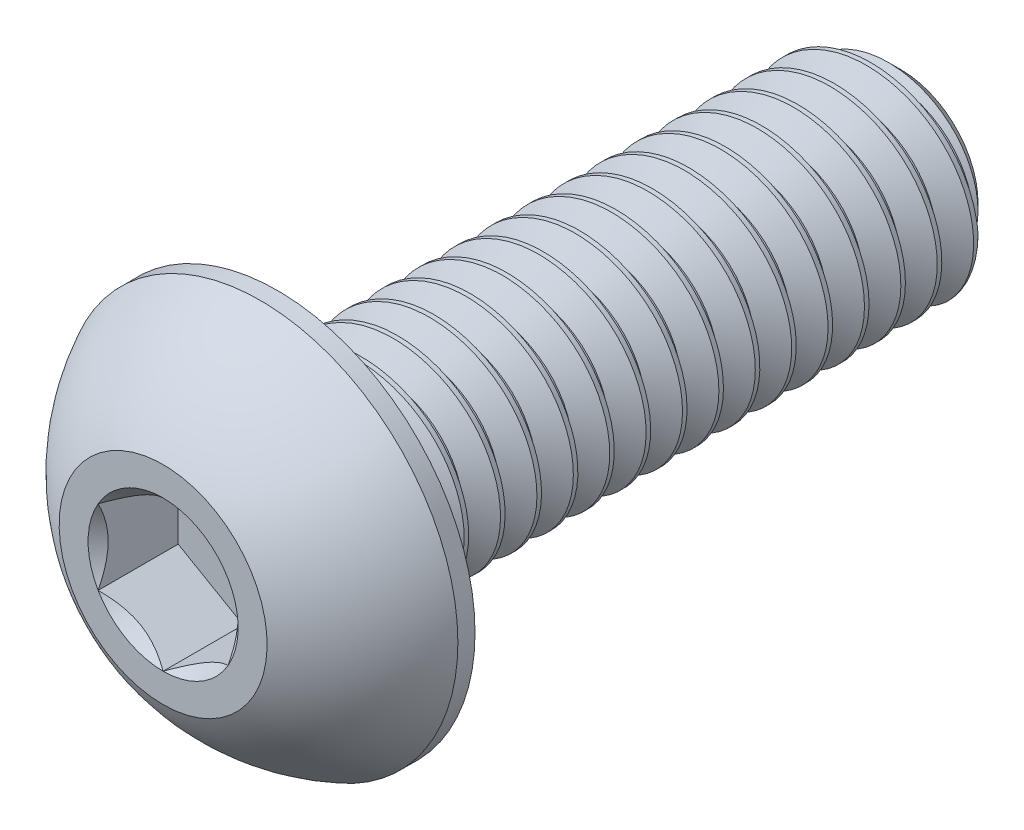
SolidWorks part; units mm, degrees
ref_plane "Front" through (0, 0, 0) normal (0, 0, 1) x (1, 0, 0)
ref_plane "Top" through (0, 0, 0) normal (0, 1, 0) x (1, 0, 0)
ref_plane "Right" through (0, 0, 0) normal (1, 0, 0) x (0, 0, -1)
sketch "Sketch1" plane through (0, 0, 0) normal (1, 0, 0) x (0, 0, -1)
  line L2 (2.2, 2) -> (14.2, 2)
  line L3 (14.2, 2) -> (14.2, 0)
  line L4 (14.2, 0) -> (2.2, 0)
  line L6 (1.87, 3.8) -> (2.2, 3.8) construction
  line L7 (14.2, 2) -> (14.2, -2) construction
  line L8 (0, 0) -> (2.2, 0) construction
  line L9 (2.2, 3.8) -> (2.2, -3.8) construction
  line L11 (2.2, 2) -> (2.2, 0)
  line L13 (0, 1.25) -> (0, -1.25) construction
  line L14 (0, 1.25) -> (0, 2) construction
  arc A3 (0, 2) -> (1.87, 3.8) centre (3.7264, 0) cw construction
  dimension "D1" = 0.33
revolve "Revolve1" add sketch "Sketch1" angle 360 mid plane about L4
sketch "Sketch3" plane through (0, 0, -14.2) normal (0, 0, -1) x (-1, 0, 0)
  circle A0 centre (0, 0) radius 2
curve "Helix/Spiral1" pitch 0.7 height 12.7 radius 2 centre (0, 0, -14.2) axis (0, 0, 1) start towards (0, 1, 0)
sketch "Sketch2" plane through (0, 0, 0) normal (1, 0, 0) x (0, 0, -1)
  line L0 (14.2, 2) -> (14.8125, 2)
  line L1 (14.8125, 2) -> (14.55, 1.5453)
  line L2 (14.55, 1.5453) -> (14.4625, 1.5453)
  line L3 (14.4625, 1.5453) -> (14.2, 2)
  line L4 (14.3313, 1.7727) -> (14.6813, 1.7727) construction
  dimension "D1" = 60
  dimension "D2" = 0.0875
  dimension "D3" = 0.35
chamfer "Chamfer1" distance 0.525 angle 45 1 edges at (0, 2, -14.2)
sweep "Cut-Sweep1" cut profiles "Sketch2" path "Helix/Spiral1" align with end faces yes
sketch "Sketch7" plane through (0, 0, 0) normal (1, 0, 0) x (0, 0, -1)
  line L6 (1.87, 3.8) -> (2.2, 3.8) construction
  line L8 (0, 0) -> (2.2, 0) construction
  line L11 (2.2, 3.8) -> (2.2, -3.8) construction
  line L12 (1.87, 3.8) -> (2.2, 3.8)
  line L13 (0, 0) -> (2.2, 0)
  line L14 (0, 1.25) -> (0, -1.25) construction
  line L15 (2.2, 3.8) -> (2.2, 0)
  line L16 (0, 2) -> (0, 0)
  arc A2 (1.87, 3.8) -> (0, 2) centre (3.7264, 0) ccw construction
  arc A3 (1.87, 3.8) -> (0, 2) centre (3.7264, 0) ccw
revolve "Revolve2" add sketch "Sketch7" angle 360 mid plane about L13
sketch "Sketch5" plane through (0, 0, 0) normal (0, 0, 1) x (1, 0, 0)
  line L1 (1.25, -0.7217) -> (1.25, 0.7217)
  line L2 (1.25, 0.7217) -> (0, 1.4434)
  line L3 (0, 1.4434) -> (-1.25, 0.7217)
  line L4 (-1.25, 0.7217) -> (-1.25, -0.7217)
  line L5 (-1.25, -0.7217) -> (0, -1.4434)
  line L6 (0, -1.4434) -> (1.25, -0.7217)
  circle A0 centre (0, 0) radius 1.25 construction
extrude "Cut-Extrude2" cut sketch "Sketch5" against normal blind 1.54
sketch "Sketch6" plane through (0, 0, 0) normal (0, 0, 1) x (1, 0, 0)
  circle A0 centre (0, 0) radius 1.4434
extrude "Cut-Extrude3" cut sketch "Sketch6" against normal blind 1.54 draft 45
sketch "Sketch9" [suppressed] plane through (0, 0, -2.2) normal (0, 0, 1) x (1, 0, 0)
  circle A2 centre (0, 0) radius 2
extrude "Boss-Extrude2" [suppressed] add sketch "Sketch9" against normal offset from surface (5 mm away) 28.575 up to face at (0, 1.475, -14.2)
sketch "Sketch10" plane through (0, 0, 0) normal (1, 0, 0) x (0, 0, -1)
  line L0 (14.2, 2) -> (14.2, -2) construction
  point P0 (13.15, -2)
  dimension "D1" = 1.05
equation "\"D3@Helix/Spiral1\" = \"Lg@Sketch1\" + \"D4@Helix/Spiral1\""
equation "\"D2@Sketch2\" = \"D4@Helix/Spiral1\" * .125"
equation "\"D3@Sketch2\" = \"D4@Helix/Spiral1\" * .5"
equation "\"D1@Chamfer1\" = \"D4@Helix/Spiral1\" * .75"
equation "\"D1@Cut-Extrude2\" = \"Head Ht@Sketch1\" * .7"
equation "\"D1@Sketch1\" = \"Head Ht@Sketch1\" * .15"
equation "\"D1@Sketch10\" = \"D4@Helix/Spiral1\" * 1.5"
equation "\"D1@Cut-Extrude3\" = \"D1@Cut-Extrude2\""
